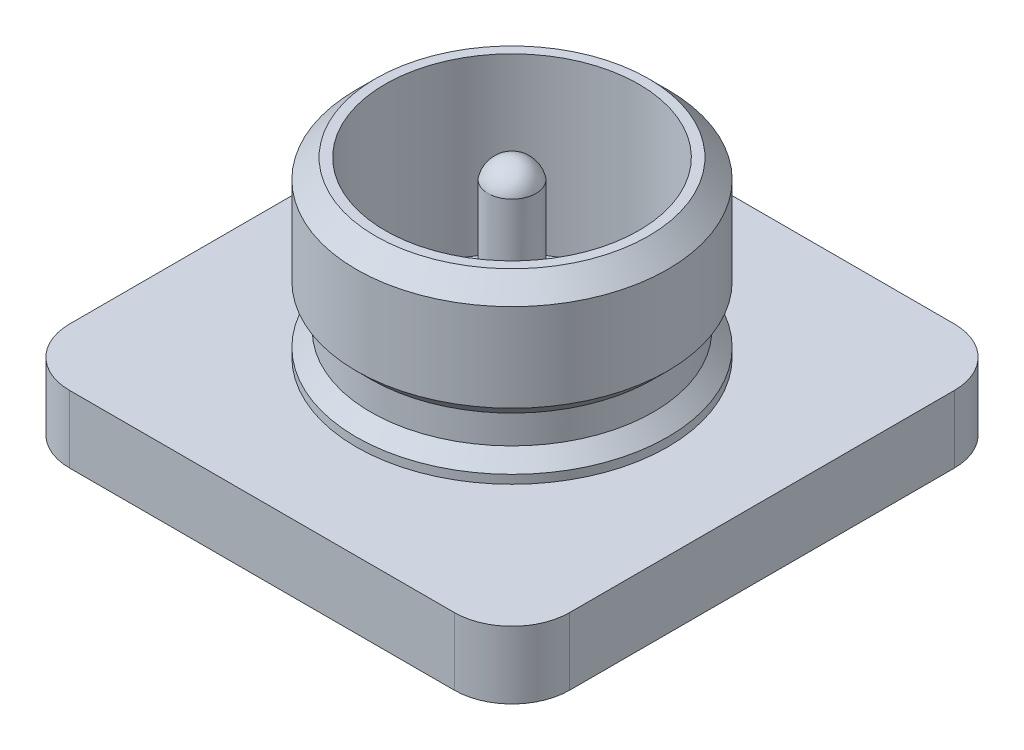
SolidWorks part; units mm, degrees
ref_plane "Front" through (0, 0, 0) normal (0, 0, 1) x (1, 0, 0)
ref_plane "Top" through (0, 0, 0) normal (0, 1, 0) x (1, 0, 0)
ref_plane "Right" through (0, 0, 0) normal (1, 0, 0) x (0, 0, -1)
sketch "Sketch1" plane through (0, 0, 0) normal (0, 1, 0) x (1, 0, 0)
  line L1 (-1.3, -1.3) -> (1.3, -1.3)
  line L2 (-1.3, -1.3) -> (-1.3, 1.3)
  line L3 (-1.3, 1.3) -> (1.3, 1.3)
  line L4 (1.3, -1.3) -> (1.3, 1.3)
  line L5 (-1.3, -1.3) -> (1.3, 1.3) construction
  line L6 (-1.3, 1.3) -> (1.3, -1.3) construction
  point P0 (0, 0)
  dimension "D1" = 2.6
  dimension "D2" = 2.6
extrude "Boss-Extrude1" add sketch "Sketch1" along normal blind 0.35
fillet "Fillet1" radius 0.3 4 edges at (-1.3, 0.175, 1.3) (1.3, 0.175, 1.3) (1.3, 0.175, -1.3) (-1.3, 0.175, -1.3)
ref_axis "Axis1" through (0, -50, 0) along (0, 1, 0)
ref_plane "Plane1" through (0, 0, 0) normal (0, 0, 1) x (1, 0, 0)
sketch "Sketch3" plane through (0, 0, 0) normal (0, 0, 1) x (1, 0, 0)
  line L0 (0.6596, 0.35) -> (0.6596, 1.25)
  line L1 (-1, 0.35) -> (1, 0.35) construction
  line L2 (0.6596, 1.25) -> (0.8096, 1.25)
  line L3 (0.8096, 1.25) -> (0.8096, 0.5925)
  line L4 (0.8096, 0.5925) -> (0.7346, 0.5925)
  line L5 (0.7346, 0.5925) -> (0.7346, 0.4947)
  line L6 (0.7346, 0.4947) -> (0.8096, 0.4947)
  line L7 (0.8096, 0.4947) -> (0.8096, 0.35)
  line L8 (0.8096, 0.35) -> (0.6596, 0.35)
  dimension "D1" = 0.9
  dimension "D2" = 0.15
  dimension "D3" = 0.075
revolve "Revolve1" add sketch "Sketch3" angle 360 about axis through (0, -50, 0) along (0, 1, 0)
chamfer "Chamfer1" distance 0.1 angle 45 1 edges at (0, 1.25, -0.8096)
chamfer "Chamfer2" distance 0.1 angle 45 2 edges at (0, 0.4947, -0.8096) (0, 0.5925, -0.8096)
sketch "Sketch4" plane through (0, 0.35, 0) normal (0, 1, 0) x (1, 0, 0)
  circle A0 centre (0, 0) radius 0.125
  dimension "D1" = 0.25
extrude "Boss-Extrude2" add sketch "Sketch4" along normal blind 0.8
dome "Dome1" faces to dome 1 distance 0.1 reverse direction no elliptical dome no face at (0, 1.15, 0.125) parameters "D1"=0.1
sketch "Sketch5" plane through (0, 0, 0) normal (0, -1, 0) x (1, 0, 0)
  circle A0 centre (0, 0) radius 0.125
  dimension "D1" = 0.25
extrude "Cut-Extrude2" cut sketch "Sketch5" against normal blind 0.34
